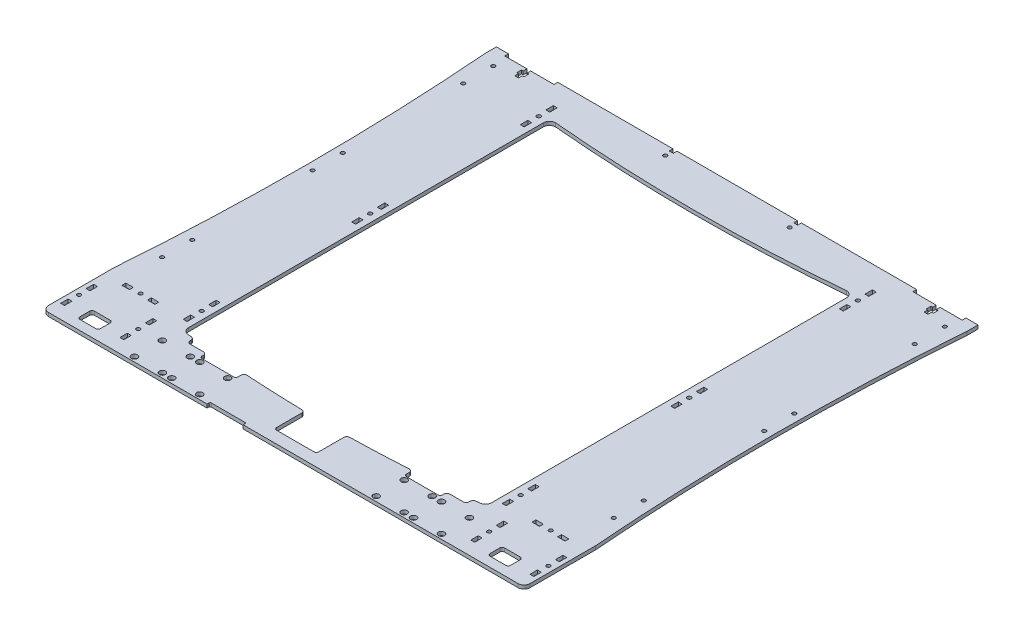
SolidWorks part; units mm, degrees
ref_plane "Alzado" through (0, 0, 0) normal (0, 0, 1) x (1, 0, 0)
ref_plane "Planta" through (0, 0, 0) normal (0, 1, 0) x (1, 0, 0)
ref_plane "Vista lateral" through (0, 0, 0) normal (1, 0, 0) x (0, 0, -1)
sketch "Croquis1" plane through (0, 0, 0) normal (0, 1, 0) x (1, 0, 0)
  line L0 (200, 377) -> (200, 0) construction
  line L1 (0, 0) -> (400, 0)
  line L2 (0, 0) -> (0, 377)
  line L3 (0, 377) -> (10, 377)
  line L4 (400, 0) -> (400, 377)
  line L5 (52.7, 17.8) -> (55.9, 17.8)
  line L6 (3.5, 17.8) -> (6.7, 17.8)
  line L7 (3.5, 17.8) -> (3.5, 11.6)
  line L8 (3.5, 11.6) -> (6.7, 11.6)
  line L9 (6.7, 17.8) -> (6.7, 11.6)
  line L10 (3.5, 39) -> (6.7, 39)
  line L11 (3.5, 39) -> (3.5, 32.8)
  line L12 (3.5, 32.8) -> (6.7, 32.8)
  line L13 (6.7, 39) -> (6.7, 32.8)
  line L14 (52.7, 17.8) -> (52.7, 11.6)
  line L15 (52.7, 11.6) -> (55.9, 11.6)
  line L16 (55.9, 17.8) -> (55.9, 11.6)
  line L17 (52.7, 39) -> (55.9, 39)
  line L18 (52.7, 39) -> (52.7, 32.8)
  line L19 (52.7, 32.8) -> (55.9, 32.8)
  line L20 (55.9, 39) -> (55.9, 32.8)
  line L21 (69.1, 218.4) -> (69.1, 212.2)
  line L22 (16, 53.2) -> (22.2, 53.2)
  line L23 (16, 53.2) -> (16, 50)
  line L24 (16, 50) -> (22.2, 50)
  line L25 (22.2, 53.2) -> (22.2, 50)
  line L26 (37.2, 53.2) -> (43.4, 53.2)
  line L27 (37.2, 53.2) -> (37.2, 50)
  line L28 (37.2, 50) -> (43.4, 50)
  line L29 (43.4, 53.2) -> (43.4, 50)
  line L30 (65.9, 57.2) -> (69.1, 57.2)
  line L31 (65.9, 57.2) -> (65.9, 51)
  line L32 (65.9, 51) -> (69.1, 51)
  line L33 (69.1, 57.2) -> (69.1, 51)
  line L34 (65.9, 78.4) -> (69.1, 78.4)
  line L35 (65.9, 78.4) -> (65.9, 72.2)
  line L36 (65.9, 72.2) -> (69.1, 72.2)
  line L37 (69.1, 78.4) -> (69.1, 72.2)
  line L38 (65.9, 218.4) -> (69.1, 218.4)
  line L39 (65.9, 218.4) -> (65.9, 212.2)
  line L40 (65.9, 212.2) -> (69.1, 212.2)
  line L41 (65.9, 197.2) -> (69.1, 197.2)
  line L42 (69.1, 197.2) -> (69.1, 191)
  line L43 (65.9, 197.2) -> (65.9, 191)
  line L44 (65.9, 191) -> (69.1, 191)
  line L45 (69.1, 78.4) -> (69.1, 218.4) construction
  line L46 (69.1, 337.2) -> (69.1, 331)
  line L47 (65.9, 337.2) -> (69.1, 337.2)
  line L48 (65.9, 337.2) -> (65.9, 331)
  line L49 (65.9, 331) -> (69.1, 331)
  line L50 (65.9, 352.2) -> (69.1, 352.2)
  line L51 (69.1, 358.4) -> (69.1, 352.2)
  line L52 (65.9, 358.4) -> (69.1, 358.4)
  line L53 (65.9, 358.4) -> (65.9, 352.2)
  line L54 (69.1, 197.2) -> (69.1, 337.2) construction
  line L55 (330.9, 197.2) -> (330.9, 337.2) construction
  line L56 (330.9, 78.4) -> (330.9, 218.4) construction
  line L57 (334.1, 358.4) -> (334.1, 352.2)
  line L58 (334.1, 358.4) -> (330.9, 358.4)
  line L59 (330.9, 358.4) -> (330.9, 352.2)
  line L60 (334.1, 352.2) -> (330.9, 352.2)
  line L61 (334.1, 331) -> (330.9, 331)
  line L62 (334.1, 337.2) -> (334.1, 331)
  line L63 (334.1, 337.2) -> (330.9, 337.2)
  line L64 (330.9, 337.2) -> (330.9, 331)
  line L65 (334.1, 191) -> (330.9, 191)
  line L66 (334.1, 197.2) -> (334.1, 191)
  line L67 (330.9, 197.2) -> (330.9, 191)
  line L68 (334.1, 197.2) -> (330.9, 197.2)
  line L69 (334.1, 212.2) -> (330.9, 212.2)
  line L70 (334.1, 218.4) -> (334.1, 212.2)
  line L71 (334.1, 218.4) -> (330.9, 218.4)
  line L72 (330.9, 78.4) -> (330.9, 72.2)
  line L73 (334.1, 72.2) -> (330.9, 72.2)
  line L74 (334.1, 78.4) -> (334.1, 72.2)
  line L75 (334.1, 78.4) -> (330.9, 78.4)
  line L76 (330.9, 57.2) -> (330.9, 51)
  line L77 (334.1, 51) -> (330.9, 51)
  line L78 (334.1, 57.2) -> (334.1, 51)
  line L79 (334.1, 57.2) -> (330.9, 57.2)
  line L80 (356.6, 53.2) -> (356.6, 50)
  line L81 (362.8, 50) -> (356.6, 50)
  line L82 (362.8, 53.2) -> (362.8, 50)
  line L83 (362.8, 53.2) -> (356.6, 53.2)
  line L84 (377.8, 53.2) -> (377.8, 50)
  line L85 (384, 50) -> (377.8, 50)
  line L86 (384, 53.2) -> (384, 50)
  line L87 (384, 53.2) -> (377.8, 53.2)
  line L88 (330.9, 218.4) -> (330.9, 212.2)
  line L89 (344.1, 39) -> (344.1, 32.8)
  line L90 (347.3, 32.8) -> (344.1, 32.8)
  line L91 (347.3, 39) -> (347.3, 32.8)
  line L92 (347.3, 39) -> (344.1, 39)
  line L93 (344.1, 17.8) -> (344.1, 11.6)
  line L94 (347.3, 11.6) -> (344.1, 11.6)
  line L95 (347.3, 17.8) -> (347.3, 11.6)
  line L96 (393.3, 39) -> (393.3, 32.8)
  line L97 (396.5, 32.8) -> (393.3, 32.8)
  line L98 (396.5, 39) -> (396.5, 32.8)
  line L99 (396.5, 39) -> (393.3, 39)
  line L100 (393.3, 17.8) -> (393.3, 11.6)
  line L101 (396.5, 11.6) -> (393.3, 11.6)
  line L102 (396.5, 17.8) -> (396.5, 11.6)
  line L103 (396.5, 17.8) -> (393.3, 17.8)
  line L104 (347.3, 17.8) -> (344.1, 17.8)
  line L105 (400, 0) -> (400, 377)
  line L106 (51, 377) -> (146.7, 377)
  line L108 (10, 377) -> (10, 373.9)
  line L109 (10, 373.9) -> (28.4, 373.9)
  line L110 (51, 377) -> (51, 373.9)
  line L111 (31.6, 373.9) -> (51, 373.9)
  line L113 (28.4, 373.9) -> (28.4, 370.9)
  line L114 (28.4, 363.9) -> (31.6, 363.9)
  line L115 (31.6, 373.9) -> (31.6, 370.9)
  line L116 (27, 370.9) -> (28.4, 370.9)
  line L117 (27, 370.9) -> (27, 366.9)
  line L118 (27, 366.9) -> (28.4, 366.9)
  line L119 (33, 370.9) -> (33, 366.9)
  line L120 (31.6, 370.9) -> (33, 370.9)
  line L121 (31.6, 366.9) -> (31.6, 363.9)
  line L122 (28.4, 366.9) -> (28.4, 363.9)
  line L123 (31.6, 366.9) -> (33, 366.9)
  line L124 (349, 377) -> (349, 373.9)
  line L125 (368.4, 373.9) -> (349, 373.9)
  line L126 (368.4, 373.9) -> (368.4, 370.9)
  line L127 (368.4, 370.9) -> (367, 370.9)
  line L128 (367, 370.9) -> (367, 366.9)
  line L129 (368.4, 366.9) -> (367, 366.9)
  line L130 (368.4, 366.9) -> (368.4, 363.9)
  line L131 (371.6, 363.9) -> (368.4, 363.9)
  line L132 (371.6, 366.9) -> (371.6, 363.9)
  line L133 (373, 366.9) -> (371.6, 366.9)
  line L134 (373, 370.9) -> (373, 366.9)
  line L135 (373, 370.9) -> (371.6, 370.9)
  line L136 (371.6, 373.9) -> (371.6, 370.9)
  line L137 (390, 373.9) -> (371.6, 373.9)
  line L138 (390, 377) -> (390, 373.9)
  line L139 (390, 377) -> (400, 377)
  line L140 (69.1, 51) -> (69.1, 0) construction
  line L141 (99.1, 31) -> (69.1, 0) construction
  line L142 (69.1, 0) -> (99.1, 0)
  line L143 (69.1, 0) -> (69.1, 31) construction
  line L144 (69.1, 31) -> (99.1, 31) construction
  line L145 (99.1, 0) -> (99.1, 31) construction
  line L146 (99.6, 0) -> (99.6, 37.4867) construction
  line L147 (72.5, 3.9) -> (95.7, 3.9) construction
  line L148 (72.5, 3.9) -> (72.5, 27.1) construction
  line L149 (72.5, 27.1) -> (95.7, 27.1) construction
  line L150 (95.7, 3.9) -> (95.7, 27.1) construction
  line L151 (72.5, 3.9) -> (95.7, 27.1) construction
  line L152 (72.5, 27.1) -> (95.7, 3.9) construction
  line L153 (150, 377) -> (250, 377)
  line L155 (146.7, 377) -> (146.7, 373.9)
  line L156 (146.7, 373.9) -> (150, 373.9)
  line L157 (150, 377) -> (150, 373.9)
  line L158 (148.35, 373.9) -> (148.35, 357.7293) construction
  line L159 (253.3, 377) -> (253.3, 373.9)
  line L160 (253.3, 373.9) -> (250, 373.9)
  line L161 (250, 377) -> (250, 373.9)
  line L162 (253.3, 377) -> (349, 377)
  line L163 (12.5, 366.9) -> (12.5, 0) construction
  circle A0 centre (5.1, 25.3) radius 1.55
  circle A1 centre (54.3, 25.3) radius 1.55
  circle A2 centre (67.5, 64.7) radius 1.6
  circle A3 centre (67.5, 204.7) radius 1.6
  circle A4 centre (67.5, 344.7) radius 1.6
  circle A5 centre (332.5, 344.7) radius 1.6
  circle A6 centre (332.5, 204.7) radius 1.6
  circle A7 centre (332.5, 64.7) radius 1.6
  circle A8 centre (345.7, 25.3) radius 1.55
  circle A9 centre (394.9, 25.3) radius 1.55
  circle A10 centre (29.7, 51.8) radius 1.55
  circle A11 centre (370.3, 51.8) radius 1.55
  circle A12 centre (72.5, 27.1) radius 2.55
  circle A13 centre (95.7, 27.1) radius 2.55
  circle A14 centre (72.5, 3.9) radius 2.55
  circle A15 centre (95.7, 3.9) radius 2.55
  circle A16 centre (327.5, 27.1) radius 2.55
  circle A17 centre (327.5, 3.9) radius 2.55
  circle A18 centre (304.3, 3.9) radius 2.55
  circle A19 centre (304.3, 27.1) radius 2.55
  circle A28 centre (103.5, 3.9) radius 2.55
  circle A29 centre (126.7, 3.9) radius 2.55
  circle A30 centre (126.7, 27.1) radius 2.55
  circle A31 centre (103.5, 27.1) radius 2.55
  circle A32 centre (273.3, 3.9) radius 2.55
  circle A33 centre (296.5, 3.9) radius 2.55
  circle A34 centre (296.5, 27.1) radius 2.55
  circle A35 centre (273.3, 27.1) radius 2.55
  circle A36 centre (148.35, 368.9) radius 1.55
  circle A37 centre (251.65, 368.9) radius 1.55
  circle A38 centre (12.5, 361.9) radius 1.55
  circle A39 centre (12.5, 336.9) radius 1.55
  circle A40 centre (12.5, 311.9) radius 1.55 [skipped]
  circle A41 centre (12.5, 286.9) radius 1.55 [skipped]
  circle A42 centre (12.5, 261.9) radius 1.55 [skipped]
  circle A43 centre (12.5, 236.9) radius 1.55
  circle A44 centre (12.5, 211.9) radius 1.55
  circle A45 centre (12.5, 186.9) radius 1.55 [skipped]
  circle A46 centre (12.5, 161.9) radius 1.55 [skipped]
  circle A48 centre (12.5, 111.9) radius 1.55
  circle A49 centre (12.5, 86.9) radius 1.55
  circle A50 centre (12.5, 136.9) radius 1.55 [skipped]
  circle A51 centre (387.5, 86.9) radius 1.55
  circle A52 centre (387.5, 111.9) radius 1.55
  circle A53 centre (387.5, 211.9) radius 1.55
  circle A54 centre (387.5, 236.9) radius 1.55
  circle A55 centre (387.5, 336.9) radius 1.55
  circle A56 centre (387.5, 361.9) radius 1.55
  point P43 (69.1, 54.1)
  point P168 (84.1, 15.5)
  point P219 (12.5, 73.9)
  dimension "D11" = 3.1
  dimension "D14" = 2
  dimension "D32" = 3.2
  dimension "D34" = 67.5
  dimension "D39" = 3.1
  dimension "D40" = 7.5
  dimension "D56" = 5.1
  dimension "D57" = 0.5
  dimension "D58" = 3.3
  dimension "D61" = 3.1
  dimension "D62" = 5
  dimension "D63" = 12.5
  dimension "D64" = 3.1
  dimension "D68" = 25
  dimension "D1" = 377
  dimension "D2" = 400
  dimension "D3" = 3.2
  dimension "D4" = 6.2
  dimension "D5" = 6.2
  dimension "D6" = 3.2
  dimension "D7" = 3.5
  dimension "D8" = 11.6
  dimension "D9" = 15
  dimension "D10" = 3.5
  dimension "D12" = 7.5
  dimension "D13" = 5.1
  dimension "D15" = 46
  dimension "D16" = 6.2
  dimension "D17" = 6.2
  dimension "D18" = 3.2
  dimension "D19" = 3.2
  dimension "D20" = 15
  dimension "D21" = 16
  dimension "D22" = 50
  dimension "D23" = 50
  dimension "D24" = 3.2
  dimension "D25" = 6.2
  dimension "D26" = 6.2
  dimension "D27" = 3.2
  dimension "D28" = 65.9
  dimension "D29" = 65.9
  dimension "D30" = 15
  dimension "D31" = 51
  dimension "D33" = 7.5
  dimension "D36" = 140
  dimension "D38" = 140
  dimension "D41" = 1.4
  dimension "D42" = 3.1
  dimension "D43" = 10
  dimension "D44" = 41
  dimension "D45" = 3.2
  dimension "D46" = 10
  dimension "D47" = 4
  dimension "D48" = 6
  dimension "D49" = 1.4
  dimension "D50" = 3
  dimension "D51" = 18.4
  dimension "D52" = 30
  dimension "D53" = 31
  dimension "D54" = 23.2
  dimension "D55" = 23.2
  dimension "D59" = 3.1
  dimension "D60" = 50
  dimension "D65" = 12
  dimension "D66" = 300
  dimension "D35" = 2
  dimension "D37" = 2
  dimension "D67" = 12
extrude "Saliente-Extruir1" add sketch "Croquis1" along normal blind 3 contours L1 L4 L3 L2 A8 A6 L57 L60 L59 L58 L34 L37 L36 L35 L30 L33 L32 L31 L26 L29 L28 L27 L22 L25 L24 L23 L17 L20 L19 L18 L5 L16 L15 L14 L10 L13 L12 L11 L6 L9
sketch "Croquis2" plane through (0, 3, 0) normal (0, 1, 0) x (1, 0, 0)
  line L0 (51, 377) -> (146.7, 377) construction
  line L1 (79.1, 347) -> (320.9, 347) construction
  line L2 (74.1, 342) -> (74.1, 47.1)
  line L3 (79.1, 42.1) -> (320.9, 42.1) construction
  line L4 (325.9, 342) -> (325.9, 47.1)
  line L5 (69.1, 337.2) -> (69.1, 331) construction
  line L6 (330.9, 337.2) -> (330.9, 331) construction
  circle A0 centre (273.3, 27.1) radius 2.55 construction
  arc A1 (325.9, 47.1) -> (320.9, 42.1) centre (320.9, 47.1) cw
  arc A2 (79.1, 347) -> (320.9, 347) centre (200, 1692.3457) ccw
  arc A3 (74.1, 342) -> (79.1, 347) centre (79.1, 342) cw
  arc A4 (320.9, 347) -> (325.9, 342) centre (320.9, 342) cw
  arc A5 (79.1, 42.1) -> (74.1, 47.1) centre (79.1, 47.1) cw
  arc A6 (79.1, 42.1) -> (320.9, 42.1) centre (200, 1082.7326) ccw
  dimension "D5" = 5
  dimension "D6" = 5
  dimension "D1" = 30
  dimension "D2" = 5
  dimension "D3" = 5
  dimension "D4" = 15
extrude "Cortar-Extruir1" cut sketch "Croquis2" against normal up to surface (3 mm away) up to face at (387.5, 0, -335.35)
fillet "Redondeo1" radius 5 2 edges at (400, 1.5, 0) (0, 1.5, 0)
sketch "Croquis4" plane through (0, 3, 0) normal (0, 1, 0) x (1, 0, 0)
  line L0 (0, 5) -> (0, 377) construction
  line L1 (0, 368) -> (6, 368) construction
  line L2 (0, 368) -> (0, 59.2)
  line L3 (0, 59.2) -> (6, 59.2) construction
  line L4 (6, 368) -> (6, 59.2) construction
  line L6 (10, 373.9) -> (28.4, 373.9) construction
  line L7 (200, 377) -> (200, 0) construction
  line L9 (150, 377) -> (250, 377) construction
  line L12 (5, 0) -> (395, 0) construction
  line L13 (400, 368) -> (400, 59.2)
  arc A0 (0, 368) -> (0, 59.2) centre (-1983.6133, 213.6) cw
  arc A2 (0, 368) -> (0, 59.2) centre (1983.6133, 213.6) ccw
  arc A3 (400, 368) -> (400, 59.2) centre (2383.6133, 213.6) ccw
  circle A4 centre (29.7, 51.8) radius 1.55 construction
  dimension "D2" = 7.4
  dimension "D1" = 5.9
  dimension "D3" = 6
extrude "Cortar-Extruir3" cut sketch "Croquis4" against normal up to surface (3 mm away) contours A0 L2 | L13 A3 up to face at (200, 0, -192.9974)
sketch "Croquis5" plane through (0, 3, 0) normal (0, 1, 0) x (1, 0, 0)
  line L0 (100.1, 29.335) -> (100.1, 41.5) construction
  line L5 (130.1, 28.5) -> (130.1, 47.9346) construction
  line L7 (200, 0) -> (200, 92.2455) construction
  line L8 (100.1, 30.5) -> (130.1, 30.5)
  line L9 (100.1, 30.5) -> (100.1, 41.5)
  line L10 (100.1, 41.5) -> (130.1, 41.5)
  line L11 (130.1, 30.5) -> (130.1, 41.5)
  line L12 (5, 0) -> (395, 0) construction
  line L13 (299.9, 30.5) -> (299.9, 41.5)
  line L14 (299.9, 30.5) -> (269.9, 30.5)
  line L15 (299.9, 41.5) -> (269.9, 41.5)
  line L16 (269.9, 30.5) -> (269.9, 41.5)
  line L17 (6.7, 17.8) -> (6.7, 11.6) construction
  line L18 (182.5, 35.2467) -> (217.5, 35.2467)
  line L19 (182.5, 35.2467) -> (182.5, 10)
  line L20 (182.5, 10) -> (217.5, 10)
  line L21 (217.5, 35.2467) -> (217.5, 10)
  line L22 (23.2, 20) -> (36.2, 20)
  line L23 (21.2, 18) -> (21.2, 10)
  line L24 (23.2, 8) -> (36.2, 8)
  line L25 (38.2, 18) -> (38.2, 10)
  line L27 (378.8, 18) -> (378.8, 10)
  line L28 (376.8, 8) -> (363.8, 8)
  line L29 (361.8, 18) -> (361.8, 10)
  line L30 (376.8, 20) -> (363.8, 20)
  arc A0 (79.1, 42.1) -> (320.9, 42.1) centre (200, 1082.7326) ccw construction
  arc A1 (23.2, 20) -> (21.2, 18) centre (23.2, 18) ccw
  arc A2 (38.2, 18) -> (36.2, 20) centre (36.2, 18) ccw
  arc A3 (36.2, 8) -> (38.2, 10) centre (36.2, 10) ccw
  arc A4 (23.2, 8) -> (21.2, 10) centre (23.2, 10) cw
  arc A5 (376.8, 20) -> (378.8, 18) centre (376.8, 18) cw
  arc A6 (376.8, 8) -> (378.8, 10) centre (376.8, 10) ccw
  arc A7 (363.8, 8) -> (361.8, 10) centre (363.8, 10) cw
  arc A8 (361.8, 18) -> (363.8, 20) centre (363.8, 18) cw
  circle A9 centre (103.5, 27.1) radius 2.55 construction
  point P36 (21.2, 20)
  point P37 (38.2, 20)
  point P40 (38.2, 8)
  dimension "D9" = 2
  dimension "D1" = 11
  dimension "D2" = 10
  dimension "D3" = 35
  dimension "D4" = 17.5
  dimension "D5" = 17
  dimension "D6" = 12
  dimension "D7" = 8
  dimension "D8" = 14.5
  dimension "D10" = 3.4
  dimension "D11" = 3.4
  dimension "D12" = 2.235
extrude "Cortar-Extruir4" cut sketch "Croquis5" against normal up to surface (3 mm away) up to face at (387.5, 0, -360.35)
fillet "Redondeo2" radius 2 6 edges at (299.9, 1.5, -30.5) (269.9, 1.5, -30.5) (100.1, 1.5, -30.5) (130.1, 1.5, -30.5) (217.5, 1.5, -10) (182.5, 1.5, -10)
sketch "Croquis6" plane through (0, 3, 0) normal (0, 1, 0) x (1, 0, 0)
  line L0 (5, 0) -> (395, 0) construction
  line L1 (136.7, 0) -> (166.7, 0)
  line L2 (136.7, 0) -> (136.7, 1.5)
  line L3 (137.7, 2.5) -> (165.7, 2.5)
  line L4 (166.7, 0) -> (166.7, 1.5)
  circle A0 centre (126.7, 3.9) radius 2.55 construction
  arc A1 (136.7, 1.5) -> (137.7, 2.5) centre (137.7, 1.5) cw
  arc A2 (165.7, 2.5) -> (166.7, 1.5) centre (165.7, 1.5) cw
  point P10 (136.7, 2.5)
  point P13 (166.7, 2.5)
  dimension "D4" = 1
  dimension "D1" = 30
  dimension "D2" = 2.5
  dimension "D3" = 10
extrude "Cortar-Extruir5" cut sketch "Croquis6" against normal up to surface (3 mm away) up to face at (200, 0, -79.5709)
sketch "Croquis7" plane through (0, 3, 0) normal (0, 1, 0) x (1, 0, 0)
  line L0 (200, 377) -> (200, 0) construction
  line L1 (150, 377) -> (250, 377) construction
  line L2 (166.7, 0) -> (395, 0) construction
  line L3 (100.1, 39.8745) -> (100.1, 32.5) construction
  line L4 (100.1, 36.0313) -> (84.1, 36.0313)
  line L5 (100.1, 36.0313) -> (100.1, 41.5313)
  line L6 (100.1, 41.5313) -> (84.1, 41.5313)
  line L7 (84.1, 36.0313) -> (84.1, 41.5313)
  line L8 (299.9, 41.5313) -> (315.9, 41.5313)
  line L9 (315.9, 36.0313) -> (315.9, 41.5313)
  line L10 (299.9, 36.0313) -> (299.9, 41.5313)
  line L11 (299.9, 36.0313) -> (315.9, 36.0313)
  arc A1 (79.1, 42.1) -> (100.1, 39.8745) centre (200, 1082.7326) ccw construction
  dimension "D1" = 5.5
  dimension "D3" = 16
extrude "Cortar-Extruir6" cut sketch "Croquis7" against normal up to surface (3 mm away) up to face at (200, 0, -79.5709)
fillet "Redondeo3" radius 2.5 10 edges at (269.9, 1.5, -37.435) (315.9, 1.5, -41.5313) (299.9, 1.5, -36.0313) (217.5, 1.5, -35.2467) (182.5, 1.5, -35.2467) (130.1, 1.5, -37.435) (100.1, 1.5, -36.0313) (84.1, 1.5, -41.5313) (315.9, 1.5, -36.0313) (84.1, 1.5, -36.0313)
